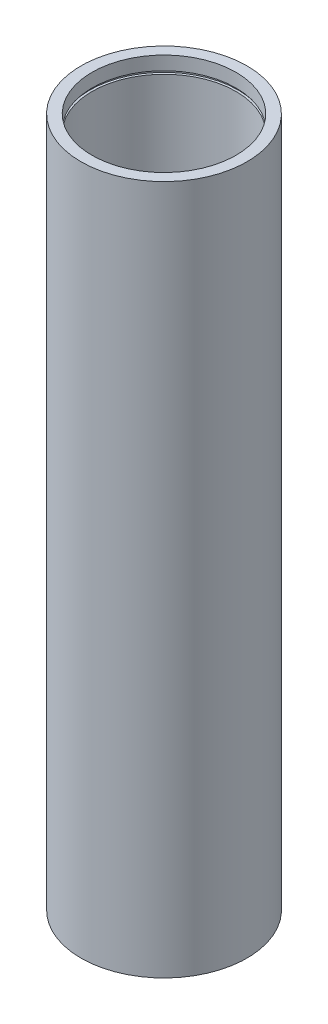
SolidWorks part; units mm, degrees
material "1060 Alloy"
ref_plane "Front Plane" through (0, 0, 0) normal (0, 0, 1) x (1, 0, 0)
ref_plane "Top Plane" through (0, 0, 0) normal (0, 1, 0) x (1, 0, 0)
ref_plane "Right Plane" through (0, 0, 0) normal (1, 0, 0) x (0, 0, -1)
sketch "Sketch2" plane through (0, 0, 0) normal (0, 0, 1) x (1, 0, 0)
  line L0 (0, 0) -> (0, 365.76) construction
  line L1 (41.275, 11.2522) -> (42.5958, 11.2522)
  line L2 (42.5958, 11.2522) -> (42.5958, 9.525)
  line L3 (41.275, 0) -> (47.625, 0)
  line L4 (41.275, 395.4526) -> (41.275, 387.6548)
  line L5 (41.275, 395.4526) -> (47.625, 395.4526)
  line L6 (47.625, 0) -> (47.625, 395.4526)
  line L7 (42.5958, 9.525) -> (41.275, 9.525)
  line L8 (41.275, 385.9276) -> (42.5958, 385.9276)
  line L9 (42.5958, 385.9276) -> (42.5958, 387.6548)
  line L10 (42.5958, 387.6548) -> (41.275, 387.6548)
  line L11 (41.275, 385.9276) -> (41.275, 11.2522)
  line L12 (41.275, 11.2522) -> (41.2565, 11.2265)
  line L13 (41.275, 9.525) -> (41.275, 0)
  line L14 (0, -55) -> (0, 55) construction
  point P18 (0, 0)
  point P19 (0, 0)
  dimension "D3" = 6.35
  dimension "D4" = 395.4526
  dimension "D5" = 9.525
  dimension "D6" = 1.7272
  dimension "D7" = 1.3208
  dimension "D8" = 9.525
  dimension "D9" = 1.3208
  dimension "D10" = 1.7272
revolve "Revolve1" add sketch "Sketch2" angle 360 about L0 region at (44.4546, 197.7247, 0)
